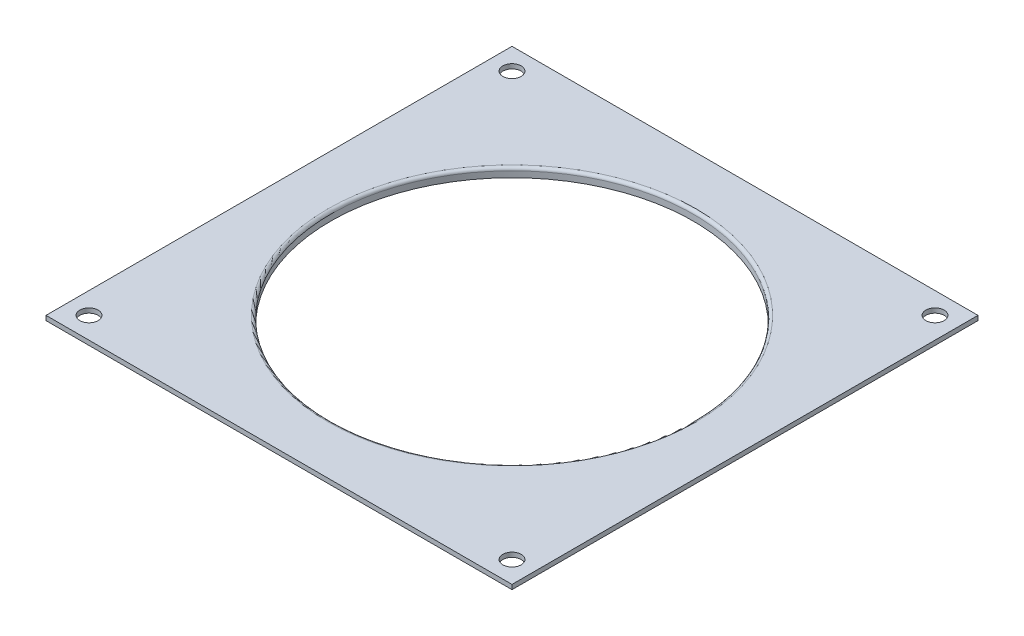
SolidWorks part; units mm, degrees
ref_plane "Alzado" through (0, 0, 0) normal (0, 0, 1) x (1, 0, 0)
ref_plane "Planta" through (0, 0, 0) normal (0, 1, 0) x (1, 0, 0)
ref_plane "Vista lateral" through (0, 0, 0) normal (1, 0, 0) x (0, 0, -1)
sketch "Croquis1" plane through (0, 0, 0) normal (0, 1, 0) x (1, 0, 0)
  line L1 (77.5, -77.5) -> (-77.5, -77.5)
  line L2 (77.5, -77.5) -> (77.5, 77.5)
  line L3 (77.5, 77.5) -> (-77.5, 77.5)
  line L4 (-77.5, -77.5) -> (-77.5, 77.5)
  line L5 (77.5, -77.5) -> (-77.5, 77.5) construction
  line L6 (77.5, 77.5) -> (-77.5, -77.5) construction
  circle A0 centre (0, 0) radius 60.3
  point P0 (0, 0)
  dimension "D3" = 120.6
  dimension "D1" = 155
  dimension "D2" = 155
extrude "Saliente-Extruir1" add sketch "Croquis1" along normal blind 8
sketch "Croquis2" plane through (0, 0, 0) normal (0, 0, 1) x (1, 0, 0)
  line L0 (77.5, 8) -> (77.5, 0) construction
  line L1 (63.0578, 6.4741) -> (73.2214, 6.4741)
  line L3 (62.8889, 1.3294) -> (77.5, 1.3294)
  line L8 (77.5, 1.3294) -> (118.6057, 1.3294)
  line L9 (0, 0) -> (0, 13.4766) construction
  line L11 (73.2214, 6.4741) -> (118.6057, 6.4741)
  line L12 (118.6057, 1.3294) -> (118.6057, 6.4741)
  arc A0 (63.0578, 6.4741) -> (62.8889, 1.3294) centre (63.7046, 3.8778) ccw
revolve "Cortar-Revolución1" cut sketch "Croquis2" angle 360 about L9
sketch "Croquis3" plane through (0, 8, 0) normal (0, 1, 0) x (1, 0, 0)
  line L4 (-77.5, 77.5) -> (-77.5, -77.5)
  line L5 (-77.5, -77.5) -> (77.5, -77.5)
  line L6 (77.5, -77.5) -> (77.5, 77.5)
  line L7 (77.5, 77.5) -> (-77.5, 77.5)
  line L9 (-77.5, -77.5) -> (77.5, -77.5)
  line L11 (77.5, 77.5) -> (-77.5, 77.5)
  line L12 (-67.3101, 70.3501) -> (-70.3501, 70.3501)
  line L13 (70.3501, -70.3501) -> (67.3101, -70.3501)
  line L14 (70.3501, -70.3501) -> (70.3501, -67.3101)
  line L15 (70.3501, 70.3501) -> (67.3101, 70.3501)
  line L16 (-70.3501, -70.3501) -> (-70.3501, -67.3101)
  line L17 (70.3501, -70.3501) -> (-70.3501, 70.3501) construction
  line L18 (70.3501, 70.3501) -> (-70.3501, -70.3501) construction
  line L19 (70.3501, 67.3101) -> (70.3501, 70.3501)
  line L20 (-67.3101, -70.3501) -> (-70.3501, -70.3501)
  line L21 (-70.3501, 67.3101) -> (-70.3501, 70.3501)
  circle A0 centre (70.3501, 70.3501) radius 3.04
  circle A1 centre (-70.3501, 70.3501) radius 3.04
  circle A2 centre (-70.3501, -70.3501) radius 3.04
  circle A3 centre (70.3501, -70.3501) radius 3.04
  point P12 (0, 0)
  dimension "D3" = 6.08
  dimension "D4" = 6.08
  dimension "D5" = 6.08
  dimension "D6" = 6.08
  dimension "D2" = 198.98
  dimension "D1" = 0
extrude "Cortar-Extruir4" cut sketch "Croquis3" against normal up to next contours A0 | A1 | A2 | A3
fillet "Redondeo1" radius 1 2 edges at (0, 0, 60.3) (0, 8, 60.3)
sketch "Croquis4" plane through (0, 0, 0) normal (0, -1, 0) x (1, 0, 0)
  circle A0 centre (-60, 60) radius 2.5
  circle A1 centre (60, 60) radius 2.5
  circle A2 centre (60, -60) radius 2.5
  circle A3 centre (-60, -60) radius 2.5
  point P0 (0, 0)
  dimension "D3" = 5
  dimension "D4" = 5
  dimension "D5" = 5
  dimension "D6" = 5
  dimension "D1" = 120
  dimension "D2" = 120
extrude "Cortar-Extruir5" cut sketch "Croquis4" against normal up to next
ref_plane "Plano1" through (0, 5, 0) normal (0, 1, 0) x (1, 0, 0)
sketch "Croquis5" plane through (0, 5, 0) normal (0, 1, 0) x (1, 0, 0)
  line L1 (80.693, -79.3953) -> (-80.693, -79.3953)
  line L2 (80.693, -79.3953) -> (80.693, 79.3953)
  line L3 (80.693, 79.3953) -> (-80.693, 79.3953)
  line L4 (-80.693, -79.3953) -> (-80.693, 79.3953)
  line L5 (80.693, -79.3953) -> (-80.693, 79.3953) construction
  line L6 (80.693, 79.3953) -> (-80.693, -79.3953) construction
  point P0 (0, 0)
extrude "Cortar-Extruir6" cut sketch "Croquis5" against normal blind 30
equation "\"D2@Croquis1\"=\"D1@Croquis1\""
